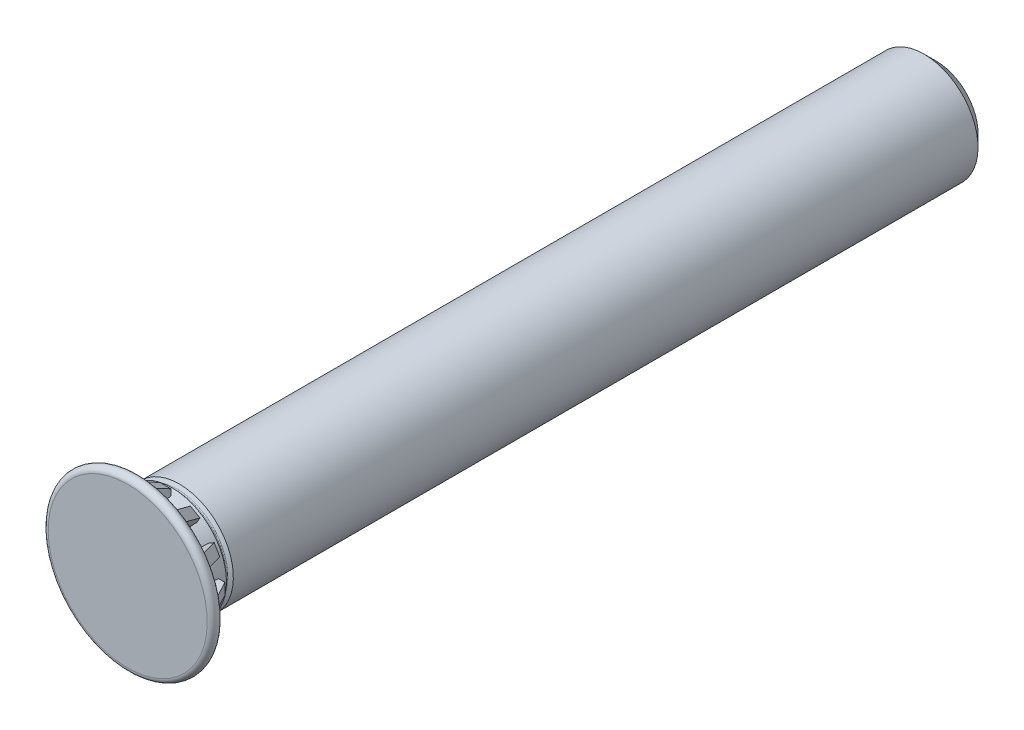
SolidWorks part; units mm, degrees
ref_plane "Front Plane" through (0, 0, 0) normal (0, 0, 1) x (1, 0, 0)
ref_plane "Top Plane" through (0, 0, 0) normal (0, 1, 0) x (1, 0, 0)
ref_plane "Right Plane" through (0, 0, 0) normal (1, 0, 0) x (0, 0, -1)
sketch "Sketch1" plane through (0, 0, 0) normal (1, 0, 0) x (0, 0, -1)
  line L0 (15, 0) -> (-15, 0) construction
  line L1 (15, 2) -> (15, -2) construction
  line L2 (-15, 3.15) -> (-15, -3.15) construction
  line L3 (15, -2) -> (-15, -2) construction
  line L4 (15, 2) -> (-15, 2) construction
  line L5 (14.9562, 2.0758) -> (15.3063, 1.4696) construction
  line L6 (15.3063, 1.4696) -> (15.6562, 2.0758) construction
  line L7 (15.6562, 2.0758) -> (14.9562, 2.0758) construction
  line L8 (15, 2) -> (15.6125, 2) construction
  line L9 (15.3062, 2.0758) -> (15.3062, 2) construction
  line L10 (15.3062, 2) -> (15.3062, 1.5453) construction
  line L11 (15.3062, 1.5453) -> (15.3063, 1.4696) construction
  line L12 (15.2625, 1.5453) -> (15.35, 1.5453)
  line L13 (14.9781, 2.0379) -> (15.6344, 2.0379)
  line L14 (15.35, 1.5453) -> (15.6344, 2.0379)
  line L15 (15.2625, 1.5453) -> (14.9781, 2.0379)
  point P8 (12.55, -2)
  point P10 (-12.6, 0)
  point P11 (-12.6, 2)
  point P24 (15.3062, 2.0379)
  point P25 (-12.6, -2)
  point P26 (-13.6, -2)
  point P28 (-13.6, 0)
  point P32 (15.3062, 1.5074)
  dimension "Thread Size" = 4
  dimension "Length" = 30
  dimension "Base Diameter" = 6.3
  dimension "Thread Pitch" = 0.7
  dimension "D3" = 0.0875
  dimension "For Minimum Material Thickness" = 1
  dimension "Unthreaded Length" = 2.4
  dimension "Thread Length" = 27.6
  dimension "D1" = 2.45
sketch "Sketch2" plane through (0, 0, 0) normal (0, 0, 1) x (1, 0, 0)
  circle A0 centre (0, 0) radius 2
sketch "Sketch7" plane through (0, 0, 0) normal (1, 0, 0) x (0, 0, -1)
  line L0 (15, 1.5453) -> (14.5453, 2)
  line L1 (15, 2) -> (15, -2) construction
  line L2 (15, 2) -> (-15, 2) construction
  line L3 (14.5453, 2) -> (-13.0816, 2)
  line L4 (-13.0816, 2) -> (-13.1691, 1.8484)
  line L5 (-13.1691, 1.8484) -> (-13.2566, 1.8484)
  line L6 (-13.2566, 1.8484) -> (-13.355, 2.0189)
  line L7 (-13.355, 2.0189) -> (-14.6, 2) construction
  line L9 (-14.6, 3.15) -> (-15, 3.15) construction
  line L11 (-15, 0) -> (15, 0)
  line L12 (15, 0) -> (15, 1.5453)
  line L13 (15.2625, 1.5453) -> (14.9781, 2.0379) construction
  line L14 (15.35, 1.5453) -> (15.6344, 2.0379) construction
  line L15 (15.2625, 1.5453) -> (15.35, 1.5453) construction
  line L16 (-15, 3.15) -> (-15, -3.15) construction
  line L17 (-14.6, 2) -> (-14.6, 2.95)
  line L18 (-15, 2.95) -> (-15, 0)
  line L19 (-13.355, 2.0189) -> (-14.6, 1.8484)
  line L20 (-14.6, 1.8484) -> (-14.6, 2)
  line L21 (14.5453, 2) -> (14.5453, 1.8484) construction
  line L22 (14.5453, 1.8484) -> (14.5453, 1.6969) construction
  line L23 (14.5453, 1.6969) -> (14.5453, 1.5453) construction
  line L24 (14.9781, 2.0379) -> (14.9781, 2) construction
  arc A0 (-14.6, 2.95) -> (-15, 2.95) centre (-14.8, 2.95) ccw
  point P10 (14.7727, 1.7727)
  point P32 (14.9781, 2.0189)
  dimension "D2" = 45
  dimension "D3" = 0.4
  dimension "D4" = 0.245
  dimension "D5" = 0.0875
revolve "Revolve3" add sketch "Sketch7" angle 360 about L0
fillet "Fillet2" radius 0.0437 2 edges at (0, 1.8484, 13.1691) (0, 1.8484, 13.2566)
sketch "Sketch16" plane through (0, 0, -15) normal (0, 0, -1) x (-1, 0, 0)
  circle A0 centre (0, 0) radius 1.5074
extrude "Cut-Extrude3" cut sketch "Sketch16" against normal blind 0.175 draft 30
sketch "Sketch13" plane through (0, 0, -14.825) normal (0, 0, -1) x (-1, 0, 0)
  circle A0 centre (0, 0) radius 0.5
  dimension "D1" = 1
extrude "Cut-Extrude1" cut sketch "Sketch13" against normal through all draft 45
sketch "Sketch9" plane through (0, 0, 0) normal (1, 0, 0) x (0, 0, -1)
  line L0 (-14.6, 2.5787) -> (-14.3, 2.5787)
  line L2 (-14.3, 2.5787) -> (-13.6, 2.2075)
  line L3 (-13.6, 2.2075) -> (-13.6, 0)
  line L4 (-13.6, 0) -> (-14.6, 0)
  line L5 (-14.6, -1.8484) -> (-14.6, 1.8484) construction
  line L6 (-14.6, 0) -> (-14.6, 2.5787)
  line L7 (-13.355, 2.0189) -> (-13.355, 2.396) construction
  line L8 (-13.355, 2.396) -> (-13.355, 2.773) construction
  line L9 (-13.6, 0) -> (0, 0) construction
  line L10 (-13.355, 2.773) -> (-13.355, 3.15) construction
  line L11 (-13.6, 2.2075) -> (-13.6, 2.95) construction
  line L12 (-14.6, 2) -> (-14.6, 2.95) construction
  point P13 (-14.45, 2.5787)
  point P18 (-13.355, 2.2075)
  point P28 (-13.6, 2.5787)
  dimension "D3" = 0.3
  dimension "D1" = 5.1575
extrude "Boss-Extrude1" add sketch "Sketch9" along normal mid plane 0.4095
pattern_circular "CirPattern3" count 12 over 360 about axis through (0, 0, -15) along (0, 0, 1) of "Boss-Extrude1"
sketch "Sketch14" plane through (0, 0, 14.6) normal (0, 0, -1) x (-1, 0, 0)
  circle A0 centre (0, 0) radius 2.3209
  dimension "D1" = 4.6417
extrude "Boss-Extrude3" add sketch "Sketch14" along normal up to vertex (0.15 mm away) up to point (0, 2.5787, 14.45)
ref_plane "Plane2" [suppressed] through (0, 0, -15) normal (0, 0, 1) x (1, 0, 0)
sketch "Sketch10" [suppressed] plane through (0, 0, -15) normal (0, 0, 1) x (1, 0, 0)
  circle A4 centre (0, 0) radius 2
curve "Helix/Spiral1" [suppressed] pitch 0.7 height 28.3 turns 40.4286
ref_plane "Plane1" [suppressed] through (0, 0, 12.6) normal (0, 0, 1) x (1, 0, 0)
split "Split1" [suppressed] bodies to split 131
sketch "Sketch11" [suppressed] plane through (0, 0, 0) normal (1, 0, 0) x (0, 0, -1)
  line L0 (15.2625, 1.5453) -> (15.35, 1.5453) construction
  line L1 (15.2625, 1.5453) -> (14.9781, 2.0379) construction
  line L2 (14.9781, 2.0379) -> (15.6344, 2.0379) construction
  line L3 (15.35, 1.5453) -> (15.6344, 2.0379) construction
  line L4 (15.2625, 1.5453) -> (15.35, 1.5453)
  line L5 (15.2625, 1.5453) -> (14.9781, 2.0379)
  line L6 (14.9781, 2.0379) -> (15.6344, 2.0379)
  line L7 (15.35, 1.5453) -> (15.6344, 2.0379)
sweep "Cut-Sweep1" [suppressed] cut profiles "Sketch11" path "Helix/Spiral1"
sketch "Sketch12" [suppressed] plane through (0, 0, 12.6) normal (0, 0, 1) x (1, 0, 0)
  circle A1 centre (0, 0) radius 2
  circle A3 centre (0, 0) radius 2
  dimension "D1" = 0
extrude "Boss-Extrude2" [suppressed] add sketch "Sketch12" against normal through all draft 55
equation "\"D3@Sketch1\" = \"Thread Pitch@Sketch1\" / 8"
equation "\"D3@Sketch7\" = \"Thread Pitch@Sketch1\" / 1.75"
equation "\"D4@Sketch7\"=\"Thread Pitch@Sketch1\" * 0.35"
equation "\"D1@Boss-Extrude1\"=\"Base Diameter@Sketch1\"*0.065"
equation "\"D4@Helix/Spiral1\" = \"Thread Pitch@Sketch1\""
equation "\"D3@Helix/Spiral1\" = \"Thread Length@Sketch1\" + \"Thread Pitch@Sketch1\""
equation "\"D1@Sketch1\" = \"Thread Pitch@Sketch1\" * 3.5"
equation "\"D1@Fillet2\"=\"D5@Sketch7\"*0.5"
equation "\"D1@Sketch13\"=\"For Hole Diameter@Sketch2\"*0.25"
equation "\"D1@Sketch14\"=\"D1@Sketch9\"*0.9"
equation "\"D3@Sketch9\"=\"D3@Sketch7\"*0.75"
equation "\"D1@Cut-Extrude3\"=\"Thread Pitch@Sketch1\"*0.25"
